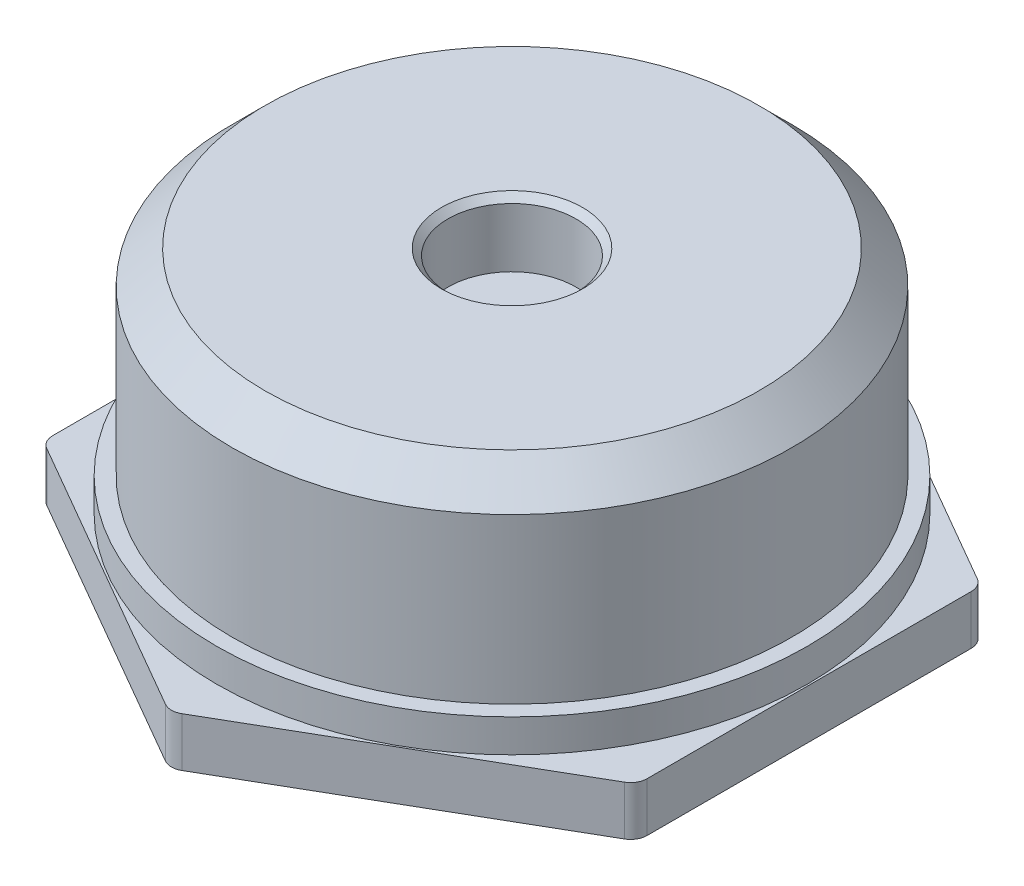
SolidWorks part; units mm, degrees
material "ABS"
ref_plane "Front Plane" through (0, 0, 0) normal (0, 0, 1) x (1, 0, 0)
ref_plane "Top Plane" through (0, 0, 0) normal (0, 1, 0) x (1, 0, 0)
ref_plane "Right Plane" through (0, 0, 0) normal (1, 0, 0) x (0, 0, -1)
ref_plane "Plane2" through (0, 31, 0) normal (0, 1, 0) x (1, 0, 0)
sketch "Sketch1" plane through (0, 31, 0) normal (0, 1, 0) x (1, 0, 0)
  line L1 (0, 10.45) -> (-9.05, 5.225)
  line L2 (-9.05, 5.225) -> (-9.05, -5.225)
  line L3 (-9.05, -5.225) -> (0, -10.45)
  line L4 (0, -10.45) -> (9.05, -5.225)
  line L5 (9.05, -5.225) -> (9.05, 5.225)
  line L6 (9.05, 5.225) -> (0, 10.45)
  circle A0 centre (0, 0) radius 9.05 construction
  dimension "D1" = 18.1
extrude "Boss-Extrude1" add sketch "Sketch1" along normal blind 1.5
fillet "Fillet1" radius 0.5 6 edges at (0, 31.75, -10.45) (-9.05, 31.75, -5.225) (-9.05, 31.75, 5.225) (0, 31.75, 10.45) (9.05, 31.75, 5.225) (9.05, 31.75, -5.225)
sketch "Sketch2" plane through (0, 32.5, 0) normal (0, 1, 0) x (1, 0, 0)
  circle A1 centre (0, 0) radius 9
  dimension "D2" = 18
extrude "Boss-Extrude2" add sketch "Sketch2" along normal blind 1 contours A1
sketch "Sketch3" plane through (0, 33.5, 0) normal (0, 1, 0) x (1, 0, 0)
  circle A0 centre (0, 0) radius 8.525
  dimension "D1" = 17.05
extrude "Boss-Extrude3" add sketch "Sketch3" along normal blind 4
sketch "Sketch4" plane through (0, 37.5, 0) normal (0, 1, 0) x (1, 0, 0)
  line L1 (0, 2.8868) -> (-2.5, 1.4434)
  line L2 (-2.5, 1.4434) -> (-2.5, -1.4434)
  line L3 (-2.5, -1.4434) -> (0, -2.8868)
  line L4 (0, -2.8868) -> (2.5, -1.4434)
  line L5 (2.5, -1.4434) -> (2.5, 1.4434)
  line L6 (2.5, 1.4434) -> (0, 2.8868)
  circle A0 centre (0, 0) radius 2.5 construction
  dimension "D1" = 5
extrude "Cut-Extrude1" cut sketch "Sketch4" against normal through all
sketch "Sketch5" plane through (0, 37.5, 0) normal (0, 1, 0) x (1, 0, 0)
  circle A0 centre (0, 0) radius 8.525
  circle A1 centre (0, 0) radius 8.525 construction
extrude "Boss-Extrude4" add sketch "Sketch5" along normal blind 1 and the other way blind 1
sketch "Sketch6" plane through (0, 38.5, 0) normal (0, 1, 0) x (1, 0, 0)
  circle A1 centre (0, 0) radius 8.525
  circle A2 centre (0, 0) radius 8.525 construction
extrude "Boss-Extrude5" add sketch "Sketch6" along normal blind 1
chamfer "Chamfer2" distance 1 angle 45 1 edges at (0, 39.5, 8.525)
sketch "Sketch7" plane through (0, 39.5, 0) normal (0, 1, 0) x (1, 0, 0)
  circle A0 centre (0, 0) radius 1.95
  dimension "D1" = 3.9
extrude "Cut-Extrude2" cut sketch "Sketch7" against normal blind 2
chamfer "Chamfer3" distance 0.2 angle 45 1 edges at (0, 39.5, 1.95)
